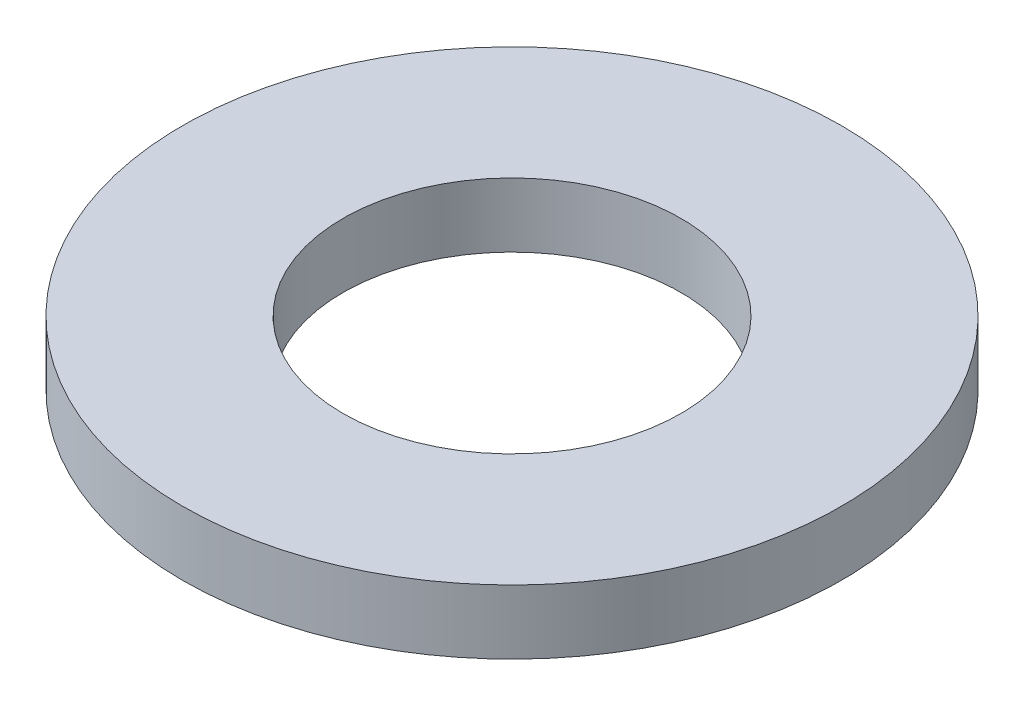
SolidWorks part; units mm, degrees
ref_plane "Front Plane" through (0, 0, 0) normal (0, 0, 1) x (1, 0, 0)
ref_plane "Top Plane" through (0, 0, 0) normal (0, 1, 0) x (1, 0, 0)
ref_plane "Right Plane" through (0, 0, 0) normal (1, 0, 0) x (0, 0, -1)
sketch "Sketch1" plane through (0, 0, 0) normal (0, 1, 0) x (1, 0, 0)
  circle A0 centre (0, 0) radius 97.5
  dimension "FLANGE_OD" = 195
extrude "Boss-Extrude1" add sketch "Sketch1" along normal blind 19
sketch "Sketch2" plane through (0, 0, 0) normal (0, 1, 0) x (1, 0, 0)
  circle A0 centre (0, 0) radius 50
  dimension "BORE_D" = 100
extrude "Cut-Extrude1" cut sketch "Sketch2" along normal through all
sketch "Sketch3" plane through (0, 19, 0) normal (0, 1, 0) x (1, 0, 0)
  circle A0 centre (0, 0) radius 40.0033 construction
  circle A1 centre (-40.0033, 0) radius 7.5945
  dimension "BOLT_D" = 15.1889
  dimension "BOLT_PCD" = 80.0066
extrude "Cut-Extrude2" cut sketch "Sketch3" against normal blind 12.4709 rebuild error yes
pattern_circular "CirPattern1" count 8 over 360 rebuild error yes
